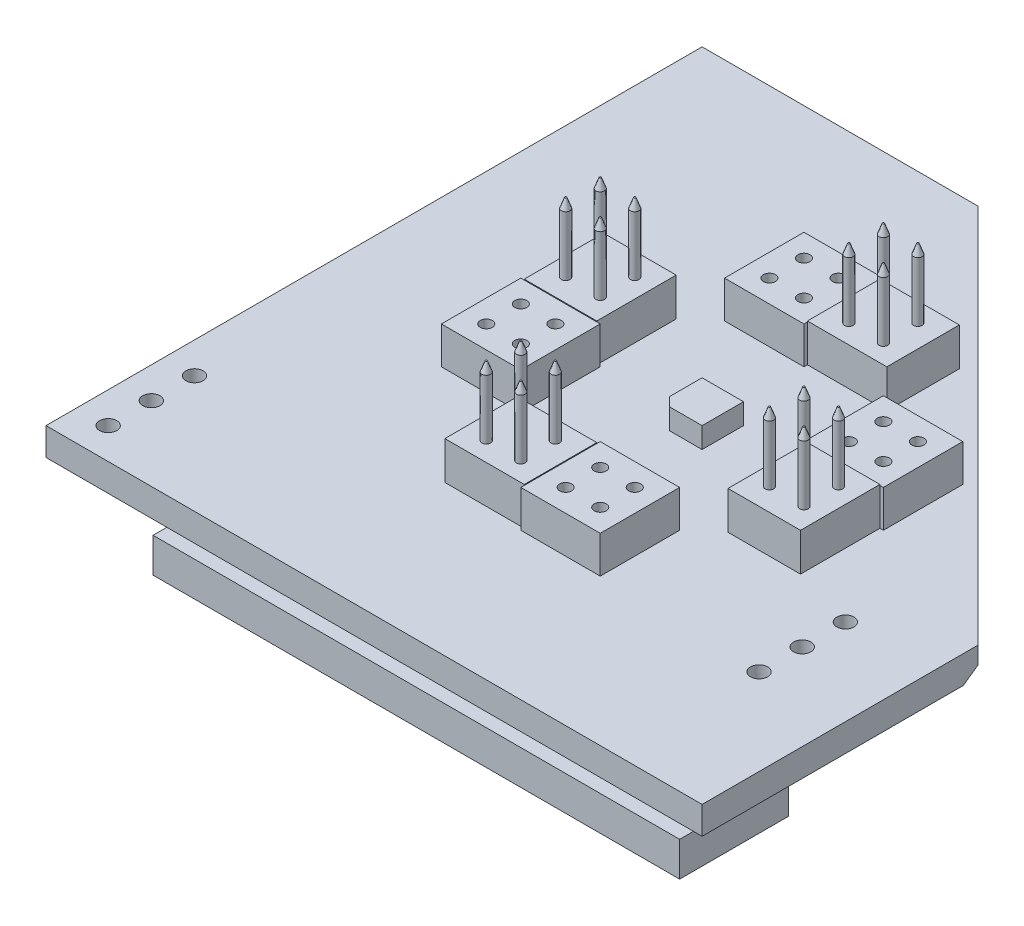
SolidWorks part; units mm, degrees
ref_plane "Front" through (0, 0, 0) normal (0, 0, 1) x (1, 0, 0)
ref_plane "Top" through (0, 0, 0) normal (0, 1, 0) x (1, 0, 0)
ref_plane "Right" through (0, 0, 0) normal (1, 0, 0) x (0, 0, -1)
sketch "Sketch1" plane through (0, 0, 0) normal (0, 1, 0) x (1, 0, 0)
  line L0 (19, -3.0194) -> (-3.0194, 19)
  line L1 (-19, 19) -> (-3.0194, 19)
  line L2 (-19, 19) -> (-19, -19)
  line L3 (-19, -19) -> (19, -19)
  line L4 (19, -3.0194) -> (19, -19)
  dimension "D1" = 19
  dimension "D2" = 19
  dimension "D3" = 19
  dimension "D4" = 19
  dimension "D5" = 45
  dimension "D6" = 11.3
extrude "Extrude1" add sketch "Sketch1" along normal blind 1.6
sketch "Sketch2" plane through (0, 1.6, 0) normal (0, 1, 0) x (-1, 0, 0)
  line L0 (-10.5, -4.6) -> (-10.5, 0)
  line L1 (4.6, -10.5) -> (0, -10.5)
  line L2 (4.6, -10.5) -> (4.6, -5.9)
  line L3 (4.6, -5.9) -> (0, -5.9)
  line L4 (0, -10.5) -> (0, -5.9)
  line L5 (-10.5, -4.6) -> (-5.9, -4.6)
  line L6 (-5.9, -4.6) -> (-5.9, 0)
  line L7 (-10.5, 0) -> (-5.9, 0)
  line L8 (-4.6, 10.5) -> (0, 10.5)
  line L9 (-4.6, 10.5) -> (-4.6, 5.9)
  line L10 (-4.6, 5.9) -> (0, 5.9)
  line L11 (0, 10.5) -> (0, 5.9)
  line L12 (10.5, 4.6) -> (10.5, 0)
  line L13 (10.5, 4.6) -> (5.9, 4.6)
  line L14 (5.9, 4.6) -> (5.9, 0)
  line L15 (10.5, 0) -> (5.9, 0)
  dimension "D1" = 4.6
  dimension "D2" = 4.6
  dimension "D3" = 5.9
  dimension "D4" = 5.9
extrude "Extrude2" add sketch "Sketch2" along normal blind 2.15
sketch "Sketch3" plane through (0, 1.6, 0) normal (0, 1, 0) x (-1, 0, 0)
  line L0 (0, -5.9) -> (0, -10.5) construction
  line L1 (-4.6, -10.3) -> (0, -10.3)
  line L2 (-4.6, -10.3) -> (-4.6, -6.1)
  line L3 (-4.6, -6.1) -> (0, -6.1)
  line L4 (0, -10.3) -> (0, -6.1)
  line L5 (-6.1, 4.6) -> (-6.1, 0)
  line L6 (-10.3, 0) -> (-6.1, 0)
  line L7 (-10.3, 4.6) -> (-6.1, 4.6)
  line L8 (-10.3, 4.6) -> (-10.3, 0)
  line L9 (4.6, 6.1) -> (0, 6.1)
  line L10 (0, 10.3) -> (0, 6.1)
  line L11 (4.6, 10.3) -> (4.6, 6.1)
  line L12 (4.6, 10.3) -> (0, 10.3)
  line L13 (6.1, -4.6) -> (6.1, 0)
  line L14 (10.3, 0) -> (6.1, 0)
  line L15 (10.3, -4.6) -> (6.1, -4.6)
  line L16 (10.3, -4.6) -> (10.3, 0)
  dimension "D1" = 4.6
  dimension "D2" = 4.2
  dimension "D3" = 6.1
  dimension "D4" = 6.1
extrude "Extrude3" add sketch "Sketch3" along normal blind 2.2
sketch "Sketch4" plane through (0, 3.75, 0) normal (0, 1, 0) x (-1, 0, 0)
  line L0 (2.3, -10.5) -> (2.3, -5.9) construction
  line L2 (4.6, -5.9) -> (0, -5.9) construction
  line L3 (4.6, -8.2) -> (0, -8.2) construction
  line L4 (0, -10.5) -> (4.6, -10.5) construction
  line L6 (4.6, -10.5) -> (4.6, -5.9) construction
  circle A0 centre (3.3, -9.2) radius 0.35
  circle A1 centre (1.3, -9.2) radius 0.35
  circle A2 centre (1.3, -7.2) radius 0.35
  circle A3 centre (3.3, -7.2) radius 0.35
  circle A4 centre (-9.2, -3.3) radius 0.35
  circle A5 centre (-9.2, -1.3) radius 0.35
  circle A6 centre (-7.2, -1.3) radius 0.35
  circle A7 centre (-7.2, -3.3) radius 0.35
  circle A8 centre (-3.3, 9.2) radius 0.35
  circle A9 centre (-1.3, 9.2) radius 0.35
  circle A10 centre (-1.3, 7.2) radius 0.35
  circle A11 centre (-3.3, 7.2) radius 0.35
  circle A12 centre (9.2, 3.3) radius 0.35
  circle A13 centre (9.2, 1.3) radius 0.35
  circle A14 centre (7.2, 1.3) radius 0.35
  circle A15 centre (7.2, 3.3) radius 0.35
  dimension "D3" = 0.7
  dimension "D1" = 1
  dimension "D2" = 1
extrude "Cut-Extrude1" cut sketch "Sketch4" against normal up to surface (2.15 mm away) up to face at (0, 1.6, 8.2)
sketch "Sketch5" plane through (0, 3.8, 0) normal (0, 1, 0) x (-1, 0, 0)
  line L0 (-2.3, -10.3) -> (-2.3, -6.1) construction
  line L1 (-4.6, -10.3) -> (0, -10.3) construction
  line L2 (0, -6.1) -> (-4.6, -6.1) construction
  line L3 (0, -8.2) -> (-4.6, -8.2) construction
  line L4 (0, -10.3) -> (0, -6.1) construction
  line L5 (-4.6, -6.1) -> (-4.6, -10.3) construction
  circle A0 centre (-1.3, -9.2) radius 0.25
  circle A1 centre (-3.3, -9.2) radius 0.25
  circle A2 centre (-3.3, -7.2) radius 0.25
  circle A3 centre (-1.3, -7.2) radius 0.25
  circle A4 centre (-7.2, 1.3) radius 0.25
  circle A5 centre (-9.2, 1.3) radius 0.25
  circle A6 centre (-9.2, 3.3) radius 0.25
  circle A7 centre (-7.2, 3.3) radius 0.25
  circle A8 centre (1.3, 7.2) radius 0.25
  circle A9 centre (1.3, 9.2) radius 0.25
  circle A10 centre (3.3, 9.2) radius 0.25
  circle A11 centre (3.3, 7.2) radius 0.25
  circle A12 centre (7.2, -1.3) radius 0.25
  circle A13 centre (9.2, -1.3) radius 0.25
  circle A14 centre (9.2, -3.3) radius 0.25
  circle A15 centre (7.2, -3.3) radius 0.25
  dimension "D3" = 0.5
  dimension "D1" = 1
  dimension "D2" = 1
extrude "Extrude4" add sketch "Sketch5" along normal blind 4
chamfer "Chamfer1" distance 0.2 angle 70 16 edges at (-1.3, 7.8, 9.45) (-3.3, 7.8, 8.95) (-3.3, 7.8, 7.45) (-1.3, 7.8, 6.95) (7.2, 7.8, 3.55) (9.2, 7.8, 3.05) (9.2, 7.8, 1.55) (7.2, 7.8, 1.05) (1.3, 7.8, -7.45) (3.3, 7.8, -6.95) (3.3, 7.8, -9.45) (1.3, 7.8, -8.95) (-9.2, 7.8, -1.05) (-7.2, 7.8, -3.05) (-9.2, 7.8, -3.55) (-7.2, 7.8, -1.55)
sketch "Sketch6" plane through (0, 0, 0) normal (0, -1, 0) x (1, 0, 0)
  line L1 (-19, 19) -> (19, 19) construction
  line L2 (19, 19) -> (19, 3.0194) construction
  line L9 (18.5, 13.5) -> (18.5, 19.8)
  line L10 (18.5, 19.8) -> (-12, 19.8)
  line L11 (-12, 19.8) -> (-12, 13.5)
  line L12 (-12, 13.5) -> (18.5, 13.5)
  dimension "D1" = 0.8
  dimension "D2" = 0.5
  dimension "D3" = 6.3
  dimension "D4" = 30.5
extrude "Extrude5" add sketch "Sketch6" along normal blind 2
sketch "Sketch7" plane through (0, 0, 0) normal (0, -1, 0) x (1, 0, 0)
  line L0 (-19, 19) -> (-12, 19) construction
  line L1 (-8.75, 3.25) -> (-1.75, 3.25)
  line L2 (-8.75, 3.25) -> (-8.75, -3.75)
  line L3 (-8.75, -3.75) -> (-1.75, -3.75)
  line L4 (-1.75, 3.25) -> (-1.75, -3.75)
  line L5 (-19, -19) -> (-19, 19) construction
  dimension "D1" = 7
  dimension "D2" = 7
  dimension "D3" = 15.75
  dimension "D4" = 10.25
extrude "Extrude6" [suppressed] add sketch "Sketch7" along normal blind 1
chamfer "Chamfer2" distance 0.6 angle 45 1 edges at (7.9903, 0, -7.9903)
sketch "Sketch8" plane through (0, 1.6, 0) normal (0, 1, 0) x (-1, 0, 0)
  line L0 (1.2, 0.7) -> (0.7, 1.2)
  line L1 (1.2, -1.2) -> (-1.2, -1.2)
  line L2 (1.2, -1.2) -> (1.2, 0.7)
  line L3 (0.7, 1.2) -> (-1.2, 1.2)
  line L4 (-1.2, -1.2) -> (-1.2, 1.2)
  dimension "D1" = 1.2
  dimension "D2" = 1.2
  dimension "D3" = 1.2
  dimension "D4" = 1.2
  dimension "D5" = 0.5
  dimension "D6" = 0.5
extrude "Extrude7" add sketch "Sketch8" along normal blind 1.2
sketch "Sketch9" plane through (0, 0, 0) normal (0, -1, 0) x (1, 0, 0)
  line L0 (19, 19) -> (19, 3.8679) construction
  line L1 (9.5, 1.7) -> (7.5, 1.7)
  line L2 (9.5, 1.7) -> (9.5, -0.3)
  line L3 (9.5, -0.3) -> (7.5, -0.3)
  line L4 (7.5, 1.7) -> (7.5, -0.3)
  line L5 (18.5, 19) -> (19, 19) construction
  line L6 (-19, 19) -> (-12, 19) construction
  line L7 (-0.35, 6.15) -> (-2.35, 6.15)
  line L8 (-0.35, 6.15) -> (-0.35, 4.15)
  line L9 (-0.35, 4.15) -> (-2.35, 4.15)
  line L10 (-2.35, 6.15) -> (-2.35, 4.15)
  dimension "D1" = 9.5
  dimension "D2" = 17.3
  dimension "D3" = 2
  dimension "D4" = 2
  dimension "D5" = 19.35
  dimension "D6" = 12.85
  dimension "D7" = 2
  dimension "D8" = 2
extrude "Extrude8" [suppressed] add sketch "Sketch9" along normal blind 0.9
sketch "Sketch10" plane through (0, 0, 0) normal (0, -1, 0) x (1, 0, 0)
  line L0 (19, 19) -> (19, 3.8679) construction
  line L1 (1.35, 2.8) -> (0.6, 2.8)
  line L2 (1.55, 2.6) -> (1.55, -0.2)
  line L3 (1.35, -0.4) -> (0.6, -0.4)
  line L4 (0.4, 2.6) -> (0.4, -0.2)
  line L5 (-19, 19) -> (-12, 19) construction
  arc A0 (0.4, -0.2) -> (0.6, -0.4) centre (0.6, -0.2) ccw
  arc A1 (0.6, 2.8) -> (0.4, 2.6) centre (0.6, 2.6) ccw
  arc A2 (1.55, 2.6) -> (1.35, 2.8) centre (1.35, 2.6) ccw
  arc A3 (1.35, -0.4) -> (1.55, -0.2) centre (1.35, -0.2) ccw
  point P10 (0.4, -0.4)
  point P15 (1.55, 2.8)
  point P18 (1.55, -0.4)
  dimension "D5" = 0.2
  dimension "D1" = 17.45
  dimension "D2" = 16.2
  dimension "D3" = 1.15
  dimension "D4" = 3.2
extrude "Extrude9" [suppressed] add sketch "Sketch10" along normal blind 1
sketch "Sketch11" plane through (0, 0, 0) normal (0, -1, 0) x (1, 0, 0)
  line L0 (19, 19) -> (19, 3.8679) construction
  line L1 (9.35, 6.9) -> (7.75, 6.9)
  line L2 (9.35, 6.9) -> (9.35, 6.1)
  line L3 (9.35, 6.1) -> (7.75, 6.1)
  line L4 (7.75, 6.9) -> (7.75, 6.1)
  line L5 (-19, 19) -> (-12, 19) construction
  line L6 (-19, -19) -> (-19, 19) construction
  line L7 (-10.15, -6.9) -> (-10.95, -6.9)
  line L8 (-10.15, -6.9) -> (-10.15, -5.3)
  line L9 (-10.15, -5.3) -> (-10.95, -5.3)
  line L10 (-10.95, -6.9) -> (-10.95, -5.3)
  line L11 (-3.8679, -19) -> (-19, -19) construction
  line L12 (-19, -19) -> (-19, 19) construction
  line L13 (-2.9, -14.85) -> (-3.7, -14.85)
  line L14 (-2.9, -14.85) -> (-2.9, -13.25)
  line L15 (-2.9, -13.25) -> (-3.7, -13.25)
  line L16 (-3.7, -14.85) -> (-3.7, -13.25)
  line L18 (-0.3, -12.1) -> (-1.1, -12.1)
  line L19 (-0.3, -12.1) -> (-0.3, -10.5)
  line L20 (-0.3, -10.5) -> (-1.1, -10.5)
  line L21 (-1.1, -12.1) -> (-1.1, -10.5)
  point P20 (-19, 0)
  point P27 (-19, 0)
  dimension "D1" = 9.65
  dimension "D2" = 12.1
  dimension "D3" = 1.6
  dimension "D4" = 0.8
  dimension "D5" = 8.05
  dimension "D6" = 12.1
  dimension "D7" = 1.6
  dimension "D8" = 0.8
  dimension "D9" = 15.3
  dimension "D10" = 4.15
  dimension "D11" = 1.6
  dimension "D12" = 0.8
  dimension "D13" = 17.9
  dimension "D14" = 6.9
  dimension "D15" = 1.6
  dimension "D16" = 0.8
extrude "Extrude10" [suppressed] add sketch "Sketch11" along normal blind 0.5
sketch "Sketch12" plane through (0, 0, 0) normal (0, -1, 0) x (1, 0, 0)
  line L0 (-19, -19) -> (-19, 19) construction
  line L1 (-11.3, -16.3) -> (-9.6, -16.3)
  line L2 (-11.3, -16.3) -> (-11.3, -12.6)
  line L3 (-11.3, -12.6) -> (-10.6, -12.6)
  line L4 (-4.6, -16.3) -> (-4.6, -12.6)
  line L5 (-3.8679, -19) -> (-19, -19) construction
  line L6 (-6.4, -16.3) -> (-4.6, -16.3)
  line L7 (-9.7, -12.6) -> (-8.45, -12.6)
  line L8 (-6.4, -16.3) -> (-6.4, -18.2)
  line L9 (-6.4, -18.2) -> (-9.6, -18.2)
  line L10 (-9.6, -16.3) -> (-9.6, -18.2)
  line L11 (-5.3, -12.6) -> (-4.6, -12.6)
  line L12 (-5.3, -12.6) -> (-5.3, -10.7)
  line L13 (-5.3, -10.7) -> (-6.2, -10.7)
  line L14 (-6.2, -12.6) -> (-6.2, -10.7)
  line L16 (-7.55, -12.6) -> (-7.55, -10.7)
  line L17 (-7.55, -10.7) -> (-8.45, -10.7)
  line L18 (-8.45, -12.6) -> (-8.45, -10.7)
  line L19 (-7.55, -12.6) -> (-6.2, -12.6)
  line L20 (-9.7, -12.6) -> (-9.7, -10.7)
  line L21 (-9.7, -10.7) -> (-10.6, -10.7)
  line L22 (-10.6, -12.6) -> (-10.6, -10.7)
  dimension "D1" = 7.7
  dimension "D2" = 2.7
  dimension "D3" = 6.7
  dimension "D4" = 3.7
  dimension "D5" = 1.9
  dimension "D6" = 3.2
  dimension "D7" = 1.7
  dimension "D8" = 0.9
  dimension "D9" = 1.9
  dimension "D10" = 0.9
  dimension "D11" = 1.9
  dimension "D12" = 0.9
  dimension "D13" = 1.9
  dimension "D14" = 2.85
  dimension "D15" = 0.7
  dimension "D16" = 0.7
extrude "Extrude11" [suppressed] add sketch "Sketch12" along normal blind 0.3
sketch "Sketch13" [suppressed] plane through (0, -0.3, 0) normal (0, -1, 0) x (1, 0, 0)
  line L1 (-4.61, -16.29) -> (-11.29, -16.29)
  line L2 (-4.61, -16.29) -> (-4.61, -12.61)
  line L3 (-4.61, -12.61) -> (-11.29, -12.61)
  line L4 (-11.29, -16.29) -> (-11.29, -12.61)
  line L5 (-6.4, -16.3) -> (-4.6, -16.3) construction
  line L6 (-4.6, -16.3) -> (-4.6, -12.6) construction
  line L7 (-11.3, -12.6) -> (-11.3, -16.3) construction
  line L8 (-10.6, -12.6) -> (-11.3, -12.6) construction
  dimension "D1" = 0.01
  dimension "D2" = 0.01
  dimension "D3" = 0.01
  dimension "D4" = 0.01
extrude "Extrude12" [suppressed] add sketch "Sketch13" along normal blind 1.5
sketch "Sketch14" plane through (0, 0, 0) normal (0, -1, 0) x (1, 0, 0)
  line L0 (-19, -19) -> (-19, 19) construction
  line L1 (-19, 19) -> (-12, 19) construction
  line L2 (-19, -19) -> (-19, 19) construction
  line L3 (18.5, 19) -> (19, 19) construction
  line L4 (19, 19) -> (19, 3.8679) construction
  circle A0 centre (-17.2, 17.2) radius 0.5
  circle A1 centre (-17.2, 14.7) radius 0.5
  circle A2 centre (-17.2, 12.2) radius 0.5
  circle A3 centre (14, 8.2) radius 0.5
  circle A4 centre (14, 5.7) radius 0.5
  circle A6 centre (14, 10.7) radius 0.5
  dimension "D1" = 1
  dimension "D5" = 5
  dimension "D7" = 5
  dimension "D8" = 1
  dimension "D2" = 1.8
  dimension "D3" = 1.8
  dimension "D4" = 1.8
  dimension "D6" = 8.3
  dimension "D9" = 5
  dimension "D10" = 5
extrude "Cut-Extrude2" cut sketch "Sketch14" against normal through all
sketch "Sketch15" plane through (0, 0, 0) normal (0, -1, 0) x (1, 0, 0)
  line L1 (19, 19) -> (19, 3.8679) construction
  line L2 (-19, -19) -> (-19, 19) construction
  circle A0 centre (14, 10.7) radius 0.5 construction
  circle A1 centre (14, 10.7) radius 0.5
  circle A2 centre (14, 10.7) radius 0.95
  circle A3 centre (14, 8.2) radius 0.5
  circle A4 centre (14, 8.2) radius 0.95
  circle A5 centre (14, 5.7) radius 0.5
  circle A6 centre (14, 5.7) radius 0.95
  circle A8 centre (-17.2, 17.2) radius 0.5 construction
  circle A10 centre (-17.2, 17.2) radius 0.5
  circle A12 centre (-17.2, 17.2) radius 0.95
  circle A14 centre (-17.2, 14.7) radius 0.5
  circle A16 centre (-17.2, 14.7) radius 0.95
  circle A18 centre (-17.2, 12.2) radius 0.5
  circle A20 centre (-17.2, 12.2) radius 0.95
  dimension "D4" = 0.45
  dimension "D1" = 0.45
  dimension "D2" = 5
  dimension "D3" = 5
  dimension "D5" = 1.8
  dimension "D6" = 5
extrude "Extrude13" add sketch "Sketch15" along normal blind 0.05 and the other way blind 1.05
sketch "Sketch16" plane through (0, 0, 0) normal (0, -1, 0) x (1, 0, 0)
  line L0 (-19, -19) -> (-19, 19) construction
  line L1 (-7.2, -8.2) -> (-10.6, -8.2)
  line L2 (-7.2, -8.2) -> (-7.2, -9.9)
  line L3 (-7.2, -9.9) -> (-10.6, -9.9)
  line L4 (-10.6, -8.2) -> (-10.6, -9.9)
  line L5 (-3.8679, -19) -> (-19, -19) construction
  dimension "D1" = 8.4
  dimension "D2" = 9.1
  dimension "D3" = 1.7
  dimension "D4" = 3.4
extrude "Extrude14" [suppressed] add sketch "Sketch16" along normal blind 1.6
sketch "Sketch17" plane through (0, 0, 0) normal (0, -1, 0) x (1, 0, 0)
  line L0 (-19, -19) -> (-19, 19) construction
  line L1 (-8.05, -5) -> (-9.25, -5)
  line L2 (-8.05, -5) -> (-8.05, -7.3)
  line L3 (-8.05, -7.3) -> (-9.25, -7.3)
  line L4 (-9.25, -5) -> (-9.25, -7.3)
  line L5 (-3.8679, -19) -> (-19, -19) construction
  point P4 (-19, 0)
  dimension "D1" = 9.75
  dimension "D2" = 11.7
  dimension "D3" = 1.2
  dimension "D4" = 2.3
extrude "Extrude15" [suppressed] add sketch "Sketch17" along normal blind 1.3
sketch "Sketch18" plane through (0, 0, 0) normal (0, -1, 0) x (1, 0, 0)
  line L0 (-19, -19) -> (-19, 19) construction
  line L1 (-3.65, -12.05) -> (-1.65, -12.05)
  line L2 (-3.65, -12.05) -> (-3.65, -11.05)
  line L3 (-3.65, -11.05) -> (-1.65, -11.05)
  line L4 (-1.65, -12.05) -> (-1.65, -11.05)
  line L5 (-3.8679, -19) -> (-19, -19) construction
  point P4 (-19, 0)
  dimension "D1" = 15.35
  dimension "D2" = 6.95
  dimension "D3" = 2
  dimension "D4" = 1
extrude "Extrude16" [suppressed] add sketch "Sketch18" along normal blind 0.5
sketch "Sketch19" plane through (0, 0, 0) normal (0, -1, 0) x (1, 0, 0)
  line L0 (-19, -19) -> (-19, 19) construction
  line L1 (-0.8, -8.45) -> (0.45, -8.45)
  line L2 (-0.8, -8.45) -> (-0.8, -7)
  line L3 (-0.8, -7) -> (-0.5, -7)
  line L4 (2.25, -8.45) -> (2.25, -7)
  line L5 (-3.8679, -19) -> (-19, -19) construction
  line L6 (1.95, -7) -> (2.25, -7)
  line L8 (0.95, -8.45) -> (0.95, -9.05)
  line L9 (0.95, -9.05) -> (0.45, -9.05)
  line L10 (0.45, -8.45) -> (0.45, -9.05)
  line L11 (0, -7) -> (1.45, -7)
  line L12 (1.95, -7) -> (1.95, -6.4)
  line L13 (1.95, -6.4) -> (1.45, -6.4)
  line L14 (1.45, -7) -> (1.45, -6.4)
  line L15 (0.95, -8.45) -> (2.25, -8.45)
  line L16 (0, -7) -> (0, -6.4)
  line L17 (0, -6.4) -> (-0.5, -6.4)
  line L18 (-0.5, -7) -> (-0.5, -6.4)
  dimension "D1" = 18.2
  dimension "D2" = 10.55
  dimension "D3" = 1.45
  dimension "D4" = 3.05
  dimension "D5" = 0.5
  dimension "D6" = 0.6
  dimension "D7" = 0.5
  dimension "D8" = 0.5
  dimension "D9" = 0.6
  dimension "D10" = 0.6
  dimension "D11" = 1.25
  dimension "D12" = 0.3
  dimension "D13" = 0.3
extrude "Extrude17" [suppressed] add sketch "Sketch19" along normal blind 0.3
sketch "Sketch20" [suppressed] plane through (0, -0.3, 0) normal (0, -1, 0) x (1, 0, 0)
  line L0 (-0.8, -7) -> (-0.8, -8.45) construction
  line L1 (-0.79, -7.01) -> (2.24, -7.01)
  line L2 (-0.79, -7.01) -> (-0.79, -8.44)
  line L3 (-0.79, -8.44) -> (2.24, -8.44)
  line L4 (2.24, -7.01) -> (2.24, -8.44)
  line L5 (-0.5, -7) -> (-0.8, -7) construction
  line L6 (-0.8, -8.45) -> (0.45, -8.45) construction
  line L7 (2.25, -8.45) -> (2.25, -7) construction
  dimension "D1" = 0.01
  dimension "D2" = 0.01
  dimension "D3" = 0.01
  dimension "D4" = 0.01
extrude "Extrude18" [suppressed] add sketch "Sketch20" along normal blind 0.8
sketch "Sketch21" plane through (0, 0, 0) normal (0, -1, 0) x (1, 0, 0)
  line L0 (-19, 19) -> (-12, 19) construction
  line L1 (4.1, 5.45) -> (0.85, 5.45)
  line L2 (4.1, 5.45) -> (4.1, 2.2)
  line L3 (4.1, 2.2) -> (0.85, 2.2)
  line L4 (0.85, 5.45) -> (0.85, 2.2)
  line L5 (19, 19) -> (19, 3.8679) construction
  dimension "D1" = 13.55
  dimension "D2" = 14.9
  dimension "D3" = 3.25
  dimension "D4" = 3.25
extrude "Extrude19" add sketch "Sketch21" along normal blind 1.1
sketch "Sketch22" plane through (0, 0, 0) normal (0, -1, 0) x (1, 0, 0)
  line L0 (19, 19) -> (19, 3.8679) construction
  line L1 (12.25, 10.9) -> (11.45, 10.9)
  line L2 (12.25, 10.9) -> (12.25, 9.3)
  line L3 (12.25, 9.3) -> (11.45, 9.3)
  line L4 (11.45, 10.9) -> (11.45, 9.3)
  line L5 (12.25, 7.4) -> (11.45, 7.4)
  line L6 (12.25, 7.4) -> (12.25, 5.8)
  line L7 (12.25, 5.8) -> (11.45, 5.8)
  line L8 (11.45, 7.4) -> (11.45, 5.8)
  line L9 (5.45, -0.65) -> (4.65, -0.65)
  line L10 (5.45, -0.65) -> (5.45, -2.25)
  line L11 (5.45, -2.25) -> (4.65, -2.25)
  line L12 (4.65, -0.65) -> (4.65, -2.25)
  line L13 (3.95, -0.65) -> (3.15, -0.65)
  line L14 (3.95, -0.65) -> (3.95, -2.25)
  line L15 (3.95, -2.25) -> (3.15, -2.25)
  line L16 (3.15, -0.65) -> (3.15, -2.25)
  line L17 (0.65, -0.15) -> (-0.15, -0.15)
  line L18 (0.65, -0.15) -> (0.65, -1.75)
  line L19 (0.65, -1.75) -> (-0.15, -1.75)
  line L20 (-0.15, -0.15) -> (-0.15, -1.75)
  line L21 (-19, 19) -> (-12, 19) construction
  line L22 (18.5, 19) -> (19, 19) construction
  line L23 (8, 3.5) -> (6, 3.5)
  line L24 (8, 3.5) -> (8, 2.2)
  line L25 (8, 2.2) -> (6, 2.2)
  line L26 (6, 3.5) -> (6, 2.2)
  dimension "D1" = 8.1
  dimension "D2" = 6.75
  dimension "D3" = 6.75
  dimension "D4" = 3.5
  dimension "D5" = 1.6
  dimension "D6" = 1.6
  dimension "D7" = 0.8
  dimension "D8" = 0.8
  dimension "D9" = 19.65
  dimension "D10" = 13.55
  dimension "D11" = 1.5
  dimension "D12" = 0.8
  dimension "D13" = 0.8
  dimension "D14" = 1.6
  dimension "D15" = 19.15
  dimension "D16" = 18.35
  dimension "D17" = 1.6
  dimension "D18" = 0.8
  dimension "D19" = 15.5
  dimension "D20" = 11
  dimension "D21" = 1.3
  dimension "D22" = 2
extrude "Extrude20" add sketch "Sketch22" along normal blind 0.5
